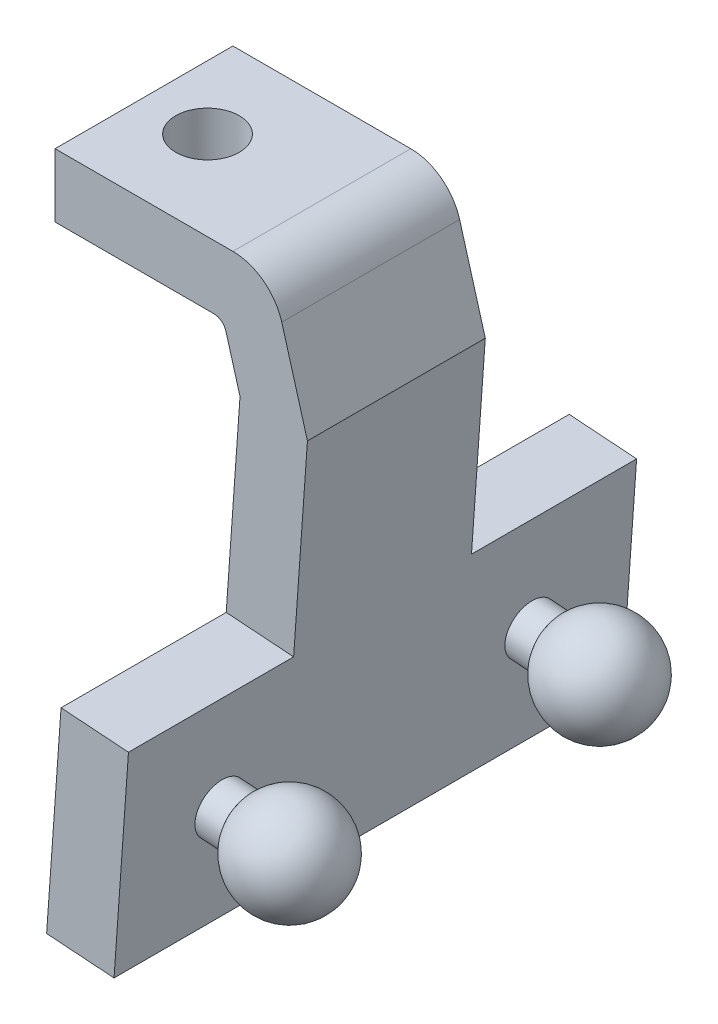
SolidWorks part; units mm, degrees
ref_plane "前视基准面" through (0, 0, 0) normal (0, 0, 1) x (1, 0, 0)
ref_plane "上视基准面" through (0, 0, 0) normal (0, 1, 0) x (1, 0, 0)
ref_plane "右视基准面" through (0, 0, 0) normal (1, 0, 0) x (0, 0, -1)
other "Configuration Table"
sketch "草图1" plane through (0, 0, 0) normal (0, 0, 1) x (1, 0, 0)
  line L0 (0, 0) -> (6.2454, 0)
  line L1 (6.7262, -0.3628) -> (7.2802, -2.304)
  line L2 (7.2802, -2.304) -> (6.1681, -17.9174)
  line L3 (6.1681, -17.9174) -> (8.8218, -18.1064)
  line L4 (8.8218, -18.1064) -> (9.9339, -2.4931)
  line L5 (9.9339, -2.4931) -> (8.9232, 1.0488)
  line L6 (0, 2.5) -> (7, 2.5)
  line L7 (0, 0) -> (0, 2.5)
  arc A0 (6.2454, 0) -> (6.7262, -0.3628) centre (6.2454, -0.5) cw
  arc A1 (8.9232, 1.0488) -> (7, 2.5) centre (7, 0.5) ccw
  dimension "D1" = 7
  dimension "D3" = 2
  dimension "D6" = 0.5
  dimension "D2" = 2.5
  dimension "D4" = 160
  dimension "D5" = 2.5
extrude "凸台-拉伸1" add sketch "草图1" along normal mid plane 7
sketch "草图2" plane through (0, 0, 0) normal (0, -1, 0) x (1, 0, 0)
  circle A0 centre (2.5, 0) radius 1.25
  dimension "D1" = 2.5
  dimension "D2" = 2.5
extrude "切除-拉伸3" cut sketch "草图2" against normal blind 5.5
sketch "草图3" plane through (10.0604, -0.7166, 0) normal (0.9975, -0.071, 0) x (0, 0, -1)
  line L0 (-3.5, -17.4339) -> (3.5, -17.4339) construction
  line L1 (-10, -9.4339) -> (10, -9.4339)
  line L2 (-10, -9.4339) -> (-10, -17.4339)
  line L3 (-10, -17.4339) -> (10, -17.4339)
  line L4 (10, -9.4339) -> (10, -17.4339)
  line L5 (-10, -9.4339) -> (10, -17.4339) construction
  line L6 (-10, -17.4339) -> (10, -9.4339) construction
  point P0 (0, -13.4339)
  dimension "D1" = 20
  dimension "D2" = 8
extrude "凸台-拉伸2" add sketch "草图3" against normal up to vertex (2.6604 mm away) up to point (7.2802, -2.304, -3.5)
sketch "草图4" plane through (10.0604, -0.7166, 0) normal (0.9975, -0.071, 0) x (0, 0, -1)
  line L0 (-10, -17.4339) -> (10, -17.4339) construction
  circle A0 centre (-6.0994, -13.4339) radius 1
  dimension "D1" = 2
  dimension "D2" = 4
extrude "凸台-拉伸3" add sketch "草图4" along normal blind 1
ref_axis "基准轴1" through (10.0985, -14.1872, 6.0994) along (-0.9975, 0.071, 0)
ref_plane "基准面1" through (-0.9544, -13.3999, 0) normal (0.071, 0.9975, 0) x (-0.9975, 0.071, 0)
sketch "草图5" plane through (-0.9544, -13.3999, 0) normal (0.071, 0.9975, 0) x (-0.9975, 0.071, 0)
  line L0 (-11.0859, 6.0994) -> (-14.818, 6.0994)
  line L1 (-11.0859, 7.0994) -> (-11.0859, 5.0994) construction
  line L2 (-11.0859, 6.0994) -> (-11.0859, 7.0994)
  arc A0 (-11.0859, 7.0994) -> (-14.818, 6.0994) centre (-12.818, 6.0994) ccw
  dimension "D1" = 4
revolve "旋转1" add sketch "草图5" angle 360 about L0
mirror "镜向1" about plane through (0, 0, 0) normal (0, 0, 1) of "凸台-拉伸3", "旋转1"
